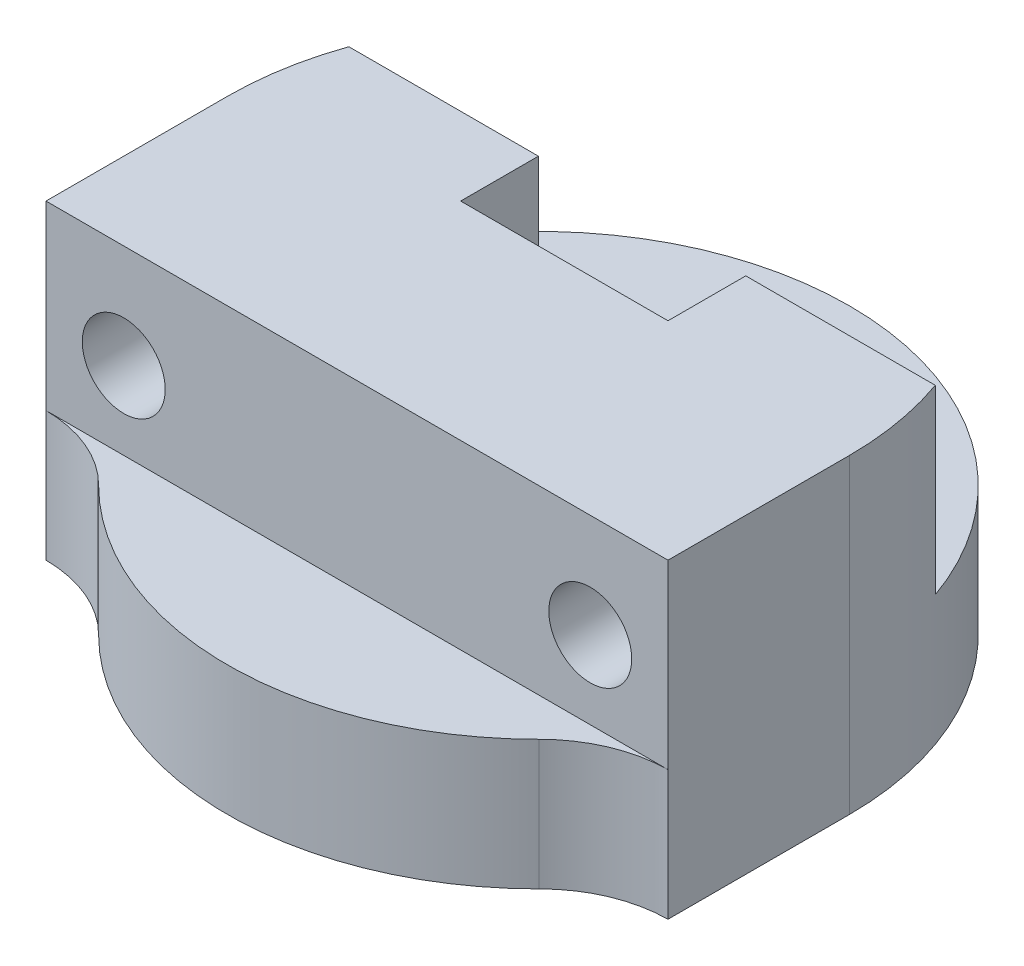
SolidWorks part; units mm, degrees
ref_plane "前视基准面" through (0, 0, 0) normal (0, 0, 1) x (1, 0, 0)
ref_plane "上视基准面" through (0, 0, 0) normal (0, 1, 0) x (1, 0, 0)
ref_plane "右视基准面" through (0, 0, 0) normal (1, 0, 0) x (0, 0, -1)
sketch "草图1" plane through (0, 0, 0) normal (0, 1, 0) x (1, 0, 0)
  line L0 (0, 0) -> (0, -20.0874) construction
  line L2 (-12, -7) -> (12, -7)
  line L3 (-12, -7) -> (-12, 0)
  line L4 (-12, 0) -> (12, 0)
  line L5 (12, -7) -> (12, 0)
  line L6 (-12, -7) -> (12, 0) construction
  line L7 (-12, 0) -> (12, -7) construction
  circle A0 centre (0, 0) radius 12
  point P3 (0, -3.5)
  point P9 (12, -7.0462)
  dimension "D1" = 24
  dimension "D2" = 7
extrude "凸台-拉伸1" add sketch "草图1" along normal blind 5 contours L4 A0 | L2 A0 L4 | A0 L3 L2 | L2 A0 | A0 L2 L5 region at (-11.3365, 0, 5.2846) region at (0, 0, 3.386) region at (0, 0, 9.0407) region at (0, 0, -5.093) region at (11.3365, 0, 5.2846)
sketch "草图2" plane through (0, 5, 0) normal (0, 1, 0) x (1, 0, 0)
  line L6 (-12, -7) -> (12, -7)
  line L8 (-12, -7) -> (-12, 4)
  line L9 (-12, 4) -> (12, 4)
  line L10 (-12, 0) -> (-12, -7)
  line L11 (-12, -7) -> (-9.7468, -7)
  line L12 (9.7468, -7) -> (12, -7)
  line L13 (12, -7) -> (12, 0)
  line L14 (-12, 0) -> (-12, -7)
  line L15 (-12, -7) -> (-9.7468, -7)
  line L16 (9.7468, -7) -> (12, -7)
  line L17 (12, -7) -> (12, 0)
  line L18 (12, -7) -> (12, 4)
  arc A4 (12, 0) -> (-12, 0) centre (0, 0) ccw
  arc A5 (-9.7468, -7) -> (9.7468, -7) centre (0, 0) ccw
  arc A6 (12, 0) -> (-12, 0) centre (0, 0) ccw
  arc A7 (-9.7468, -7) -> (9.7468, -7) centre (0, 0) ccw
  point P3 (12.2272, -7)
  dimension "D1" = 4
  dimension "D2" = 0
extrude "凸台-拉伸2" add sketch "草图2" along normal blind 7 contours L17 A6 L9 L8 L6 region at (0, 5, 1.5311)
sketch "草图3" plane through (0, 0, 0) normal (0, -1, 0) x (1, 0, 0)
  line L0 (0, 0) -> (9, 0) construction
  line L1 (0, -0.1722) -> (0, 5.6691) construction
  circle A0 centre (9, 0) radius 1.5
  circle A1 centre (-9, 0) radius 1.5
  dimension "D1" = 3
  dimension "D2" = 18
extrude "切除-拉伸1" cut sketch "草图3" against normal blind 10
sketch "草图4" plane through (0, 0, 7) normal (0, 0, 1) x (1, 0, 0)
  line L0 (7.5, 10) -> (10.5, 10) construction
  line L1 (7.5, 10) -> (10.5, 10) construction
  line L2 (9, 10) -> (9, -6.3726) construction
  line L4 (0, 0) -> (0, 21.9219) construction
  line L6 (-9.7468, 5) -> (9.7468, 5) construction
  line L7 (-9.7468, 5) -> (9.7468, 5) construction
  circle A0 centre (9, 8) radius 1.6
  circle A1 centre (-9, 8) radius 1.6
  point P4 (9, -6.3726)
  point P15 (9, 11.3593)
  point P16 (0, 0)
  point P17 (0, 0)
  dimension "D1" = 3.2
  dimension "D2" = 3
extrude "切除-拉伸2" cut sketch "草图4" against normal blind 3.5
sketch "草图5" plane through (0, 12, 0) normal (0, 1, 0) x (1, 0, 0)
  line L0 (0, 0) -> (0, -6.2126) construction
  line L2 (-4, 5) -> (4, 5)
  line L3 (-4, 5) -> (-4, 1)
  line L4 (-4, 1) -> (4, 1)
  line L5 (4, 5) -> (4, 1)
  line L6 (-4, 5) -> (4, 1) construction
  line L7 (-4, 1) -> (4, 5) construction
  line L8 (-11.3137, 4) -> (11.3137, 4) construction
  point P3 (0, 3)
  point P8 (3.5, -4.8932)
  point P9 (0, 0)
  point P10 (0, 0)
  point P11 (0, 0)
  point P12 (4, 0.7691)
  dimension "D1" = 8
  dimension "D2" = 1
  dimension "D3" = 4
extrude "切除-拉伸4" cut sketch "草图5" against normal through all
fillet "圆角1" radius 5 2 edges at (9.7468, 2.5, 7) (-9.7468, 2.5, 7)
